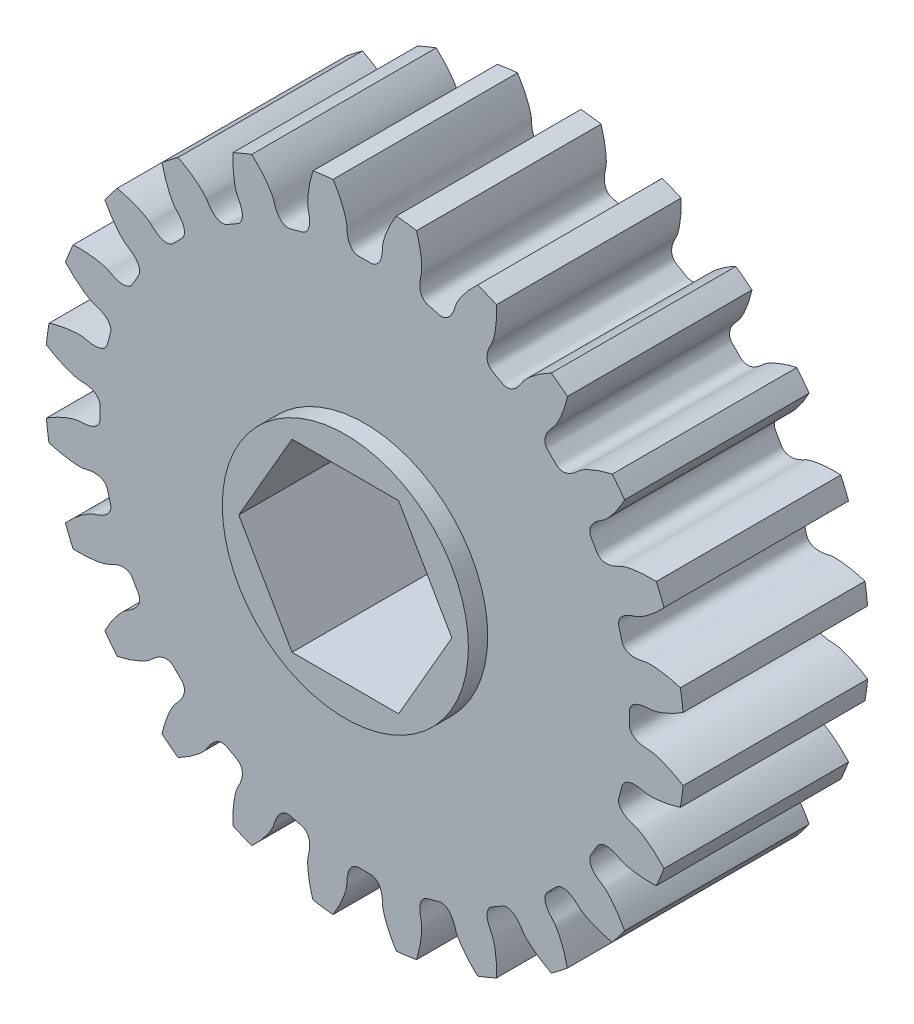
SolidWorks part; units mm, degrees
material "7075-T6 (SN)"
ref_plane "Front Plane" through (0, 0, 0) normal (0, 0, 1) x (1, 0, 0)
ref_plane "Top Plane" through (0, 0, 0) normal (0, 1, 0) x (1, 0, 0)
ref_plane "Right Plane" through (0, 0, 0) normal (1, 0, 0) x (0, 0, -1)
ref_plane "Plane1" through (0, 0, -5.715) normal (0, 0, -1) x (-1, 0, 0)
sketch "Sketch1" plane through (0, 0, -5.715) normal (0, 0, -1) x (-1, 0, 0)
  arc A0 (-12.7729, 10.461) -> (-13.4104, 9.6302) centre (0, 0) ccw
  arc A1 (-15.0452, 6.7987) -> (-15.446, 5.8312) centre (0, 0) ccw
  arc A2 (-16.2922, 2.673) -> (-16.4289, 1.6348) centre (0, 0) ccw
  arc A3 (-16.4289, -1.6348) -> (-16.2922, -2.673) centre (0, 0) ccw
  arc A4 (-15.446, -5.8312) -> (-15.0452, -6.7987) centre (0, 0) ccw
  arc A5 (-13.4104, -9.6302) -> (-12.7729, -10.461) centre (0, 0) ccw
  arc A6 (-10.461, -12.7729) -> (-9.6302, -13.4104) centre (0, 0) ccw
  arc A7 (-6.7987, -15.0452) -> (-5.8312, -15.446) centre (0, 0) ccw
  arc A8 (-2.673, -16.2922) -> (-1.6348, -16.4289) centre (0, 0) ccw
  arc A9 (1.6348, -16.4289) -> (2.673, -16.2922) centre (0, 0) ccw
  arc A10 (5.8312, -15.446) -> (6.7987, -15.0452) centre (0, 0) ccw
  arc A11 (9.6302, -13.4104) -> (10.461, -12.7729) centre (0, 0) ccw
  arc A12 (12.7729, -10.461) -> (13.4104, -9.6302) centre (0, 0) ccw
  arc A13 (15.0452, -6.7987) -> (15.446, -5.8312) centre (0, 0) ccw
  arc A14 (16.2922, -2.673) -> (16.4289, -1.6348) centre (0, 0) ccw
  arc A15 (16.4289, 1.6348) -> (16.2922, 2.673) centre (0, 0) ccw
  arc A16 (15.446, 5.8312) -> (15.0452, 6.7987) centre (0, 0) ccw
  arc A17 (13.4104, 9.6302) -> (12.7729, 10.461) centre (0, 0) ccw
  arc A18 (10.461, 12.7729) -> (9.6302, 13.4104) centre (0, 0) ccw
  arc A19 (6.7987, 15.0452) -> (5.8312, 15.446) centre (0, 0) ccw
  arc A20 (2.673, 16.2922) -> (1.6348, 16.4289) centre (0, 0) ccw
  arc A21 (-1.6348, 16.4289) -> (-2.673, 16.2922) centre (0, 0) ccw
  arc A22 (-5.8312, 15.446) -> (-6.7987, 15.0452) centre (0, 0) ccw
  arc A23 (-9.6302, 13.4104) -> (-10.461, 12.7729) centre (0, 0) ccw
  spline S0 degree 3 number of poles 101 (-15.0452, 6.7987) -> (-13.4104, 9.6302)
  spline S1 degree 3 number of poles 101 (-16.2922, 2.673) -> (-15.446, 5.8312)
  spline S2 degree 3 number of poles 101 (-16.4289, -1.6348) -> (-16.4289, 1.6348)
  spline S3 degree 3 number of poles 101 (-15.446, -5.8312) -> (-16.2922, -2.673)
  spline S4 degree 3 number of poles 101 (-13.4104, -9.6302) -> (-15.0452, -6.7987)
  spline S5 degree 3 number of poles 101 (-10.461, -12.7729) -> (-12.7729, -10.461)
  spline S6 degree 3 number of poles 101 (-6.7987, -15.0452) -> (-9.6302, -13.4104)
  spline S7 degree 3 number of poles 101 (-2.673, -16.2922) -> (-5.8312, -15.446)
  spline S8 degree 3 number of poles 101 (1.6348, -16.4289) -> (-1.6348, -16.4289)
  spline S9 degree 3 number of poles 101 (5.8312, -15.446) -> (2.673, -16.2922)
  spline S10 degree 3 number of poles 101 (9.6302, -13.4104) -> (6.7987, -15.0452)
  spline S11 degree 3 number of poles 101 (12.7729, -10.461) -> (10.461, -12.7729)
  spline S12 degree 3 number of poles 101 (15.0452, -6.7987) -> (13.4104, -9.6302)
  spline S13 degree 3 number of poles 101 (16.2922, -2.673) -> (15.446, -5.8312)
  spline S14 degree 3 number of poles 101 (16.4289, 1.6348) -> (16.4289, -1.6348)
  spline S15 degree 3 number of poles 101 (15.446, 5.8312) -> (16.2922, 2.673)
  spline S16 degree 3 number of poles 101 (13.4104, 9.6302) -> (15.0452, 6.7987)
  spline S17 degree 3 number of poles 101 (10.461, 12.7729) -> (12.7729, 10.461)
  spline S18 degree 3 number of poles 101 (6.7987, 15.0452) -> (9.6302, 13.4104)
  spline S19 degree 3 number of poles 101 (2.673, 16.2922) -> (5.8312, 15.446)
  spline S20 degree 3 number of poles 101 (-1.6348, 16.4289) -> (1.6348, 16.4289)
  spline S21 degree 3 number of poles 101 (-5.8312, 15.446) -> (-2.673, 16.2922)
  spline S22 degree 3 number of poles 101 (-9.6302, 13.4104) -> (-6.7987, 15.0452)
  spline S23 degree 3 number of poles 101 (-12.7729, 10.461) -> (-10.461, 12.7729)
extrude "Boss-Extrude1" add sketch "Sketch1" against normal blind 11.43
sketch "Sketch3" plane through (0, 0, 5.715) normal (0, 0, 1) x (1, 0, 0)
  circle A0 centre (0, 0) radius 6.35
  dimension "D1" = 12.7
extrude "Boss-Extrude3" add sketch "Sketch3" along normal blind 0.6096
sketch "Sketch4" plane through (0, 0, 6.3246) normal (0, 0, 1) x (1, 0, 0)
  line L1 (2.7496, 4.7625) -> (-2.7496, 4.7625)
  line L2 (-2.7496, 4.7625) -> (-5.4993, 0)
  line L3 (-5.4993, 0) -> (-2.7496, -4.7625)
  line L4 (-2.7496, -4.7625) -> (2.7496, -4.7625)
  line L5 (2.7496, -4.7625) -> (5.4993, 0)
  line L6 (5.4993, 0) -> (2.7496, 4.7625)
  circle A2 centre (0, 0) radius 4.7625 construction
  dimension "D1" = 9.525
extrude "Cut-Extrude1" cut sketch "Sketch4" against normal through all
sketch "Sketch5" plane through (0, 0, 6.3246) normal (0, 0, 1) x (1, 0, 0)
  arc A24 (10.461, 12.7729) -> (9.6302, 13.4104) centre (0, 0) ccw
  arc A25 (6.7987, 15.0452) -> (5.8312, 15.446) centre (0, 0) ccw
  arc A26 (2.673, 16.2922) -> (1.6348, 16.4289) centre (0, 0) ccw
  arc A27 (-1.6348, 16.4289) -> (-2.673, 16.2922) centre (0, 0) ccw
  arc A28 (-5.8312, 15.446) -> (-6.7987, 15.0452) centre (0, 0) ccw
  arc A29 (-9.6302, 13.4104) -> (-10.461, 12.7729) centre (0, 0) ccw
  arc A30 (-12.7729, 10.461) -> (-13.4104, 9.6302) centre (0, 0) ccw
  arc A31 (-15.0452, 6.7987) -> (-15.446, 5.8312) centre (0, 0) ccw
  arc A32 (-16.2922, 2.673) -> (-16.4289, 1.6348) centre (0, 0) ccw
  arc A33 (-16.4289, -1.6348) -> (-16.2922, -2.673) centre (0, 0) ccw
  arc A34 (-15.446, -5.8312) -> (-15.0452, -6.7987) centre (0, 0) ccw
  arc A35 (-13.4104, -9.6302) -> (-12.7729, -10.461) centre (0, 0) ccw
  arc A36 (-10.461, -12.7729) -> (-9.6302, -13.4104) centre (0, 0) ccw
  arc A37 (-6.7987, -15.0452) -> (-5.8312, -15.446) centre (0, 0) ccw
  arc A38 (-2.673, -16.2922) -> (-1.6348, -16.4289) centre (0, 0) ccw
  arc A39 (1.6348, -16.4289) -> (2.673, -16.2922) centre (0, 0) ccw
  arc A40 (5.8312, -15.446) -> (6.7987, -15.0452) centre (0, 0) ccw
  arc A41 (9.6302, -13.4104) -> (10.461, -12.7729) centre (0, 0) ccw
  arc A42 (12.7729, -10.461) -> (13.4104, -9.6302) centre (0, 0) ccw
  arc A43 (15.0452, -6.7987) -> (15.446, -5.8312) centre (0, 0) ccw
  arc A44 (16.2922, -2.673) -> (16.4289, -1.6348) centre (0, 0) ccw
  arc A45 (16.4289, 1.6348) -> (16.2922, 2.673) centre (0, 0) ccw
  arc A46 (15.446, 5.8312) -> (15.0452, 6.7987) centre (0, 0) ccw
  arc A47 (13.4104, 9.6302) -> (12.7729, 10.461) centre (0, 0) ccw
  arc A48 (10.461, 12.7729) -> (9.6302, 13.4104) centre (0, 0) ccw
  arc A49 (6.7987, 15.0452) -> (5.8312, 15.446) centre (0, 0) ccw
  arc A50 (2.673, 16.2922) -> (1.6348, 16.4289) centre (0, 0) ccw
  arc A51 (-1.6348, 16.4289) -> (-2.673, 16.2922) centre (0, 0) ccw
  arc A52 (-5.8312, 15.446) -> (-6.7987, 15.0452) centre (0, 0) ccw
  arc A53 (-9.6302, 13.4104) -> (-10.461, 12.7729) centre (0, 0) ccw
  arc A54 (-12.7729, 10.461) -> (-13.4104, 9.6302) centre (0, 0) ccw
  arc A55 (-15.0452, 6.7987) -> (-15.446, 5.8312) centre (0, 0) ccw
  arc A56 (-16.2922, 2.673) -> (-16.4289, 1.6348) centre (0, 0) ccw
  arc A57 (-16.4289, -1.6348) -> (-16.2922, -2.673) centre (0, 0) ccw
  arc A58 (-15.446, -5.8312) -> (-15.0452, -6.7987) centre (0, 0) ccw
  arc A59 (-13.4104, -9.6302) -> (-12.7729, -10.461) centre (0, 0) ccw
  arc A60 (-10.461, -12.7729) -> (-9.6302, -13.4104) centre (0, 0) ccw
  arc A61 (-6.7987, -15.0452) -> (-5.8312, -15.446) centre (0, 0) ccw
  arc A62 (-2.673, -16.2922) -> (-1.6348, -16.4289) centre (0, 0) ccw
  arc A63 (1.6348, -16.4289) -> (2.673, -16.2922) centre (0, 0) ccw
  arc A64 (5.8312, -15.446) -> (6.7987, -15.0452) centre (0, 0) ccw
  arc A65 (9.6302, -13.4104) -> (10.461, -12.7729) centre (0, 0) ccw
  arc A66 (12.7729, -10.461) -> (13.4104, -9.6302) centre (0, 0) ccw
  arc A67 (15.0452, -6.7987) -> (15.446, -5.8312) centre (0, 0) ccw
  arc A68 (16.2922, -2.673) -> (16.4289, -1.6348) centre (0, 0) ccw
  arc A69 (16.4289, 1.6348) -> (16.2922, 2.673) centre (0, 0) ccw
  arc A70 (15.446, 5.8312) -> (15.0452, 6.7987) centre (0, 0) ccw
  arc A71 (13.4104, 9.6302) -> (12.7729, 10.461) centre (0, 0) ccw
  spline S24 degree 3 number of poles 101 (12.7729, 10.461) -> (10.461, 12.7729)
  spline S25 degree 3 number of poles 101 (9.6302, 13.4104) -> (6.7987, 15.0452)
  spline S26 degree 3 number of poles 101 (5.8312, 15.446) -> (2.673, 16.2922)
  spline S27 degree 3 number of poles 101 (1.6348, 16.4289) -> (-1.6348, 16.4289)
  spline S28 degree 3 number of poles 101 (-2.673, 16.2922) -> (-5.8312, 15.446)
  spline S29 degree 3 number of poles 101 (-6.7987, 15.0452) -> (-9.6302, 13.4104)
  spline S30 degree 3 number of poles 101 (-10.461, 12.7729) -> (-12.7729, 10.461)
  spline S31 degree 3 number of poles 101 (-13.4104, 9.6302) -> (-15.0452, 6.7987)
  spline S32 degree 3 number of poles 101 (-15.446, 5.8312) -> (-16.2922, 2.673)
  spline S33 degree 3 number of poles 101 (-16.4289, 1.6348) -> (-16.4289, -1.6348)
  spline S34 degree 3 number of poles 101 (-16.2922, -2.673) -> (-15.446, -5.8312)
  spline S35 degree 3 number of poles 101 (-15.0452, -6.7987) -> (-13.4104, -9.6302)
  spline S36 degree 3 number of poles 101 (-12.7729, -10.461) -> (-10.461, -12.7729)
  spline S37 degree 3 number of poles 101 (-9.6302, -13.4104) -> (-6.7987, -15.0452)
  spline S38 degree 3 number of poles 101 (-5.8312, -15.446) -> (-2.673, -16.2922)
  spline S39 degree 3 number of poles 101 (-1.6348, -16.4289) -> (1.6348, -16.4289)
  spline S40 degree 3 number of poles 101 (2.673, -16.2922) -> (5.8312, -15.446)
  spline S41 degree 3 number of poles 101 (6.7987, -15.0452) -> (9.6302, -13.4104)
  spline S42 degree 3 number of poles 101 (10.461, -12.7729) -> (12.7729, -10.461)
  spline S43 degree 3 number of poles 101 (13.4104, -9.6302) -> (15.0452, -6.7987)
  spline S44 degree 3 number of poles 101 (15.446, -5.8312) -> (16.2922, -2.673)
  spline S45 degree 3 number of poles 101 (16.4289, -1.6348) -> (16.4289, 1.6348)
  spline S46 degree 3 number of poles 101 (16.2922, 2.673) -> (15.446, 5.8312)
  spline S47 degree 3 number of poles 101 (15.0452, 6.7987) -> (13.4104, 9.6302)
  spline S48 degree 3 number of poles 101 (12.7729, 10.461) -> (10.461, 12.7729)
  spline S49 degree 3 number of poles 101 (9.6302, 13.4104) -> (6.7987, 15.0452)
  spline S50 degree 3 number of poles 101 (5.8312, 15.446) -> (2.673, 16.2922)
  spline S51 degree 3 number of poles 101 (1.6348, 16.4289) -> (-1.6348, 16.4289)
  spline S52 degree 3 number of poles 101 (-2.673, 16.2922) -> (-5.8312, 15.446)
  spline S53 degree 3 number of poles 101 (-6.7987, 15.0452) -> (-9.6302, 13.4104)
  spline S54 degree 3 number of poles 101 (-10.461, 12.7729) -> (-12.7729, 10.461)
  spline S55 degree 3 number of poles 101 (-13.4104, 9.6302) -> (-15.0452, 6.7987)
  spline S56 degree 3 number of poles 101 (-15.446, 5.8312) -> (-16.2922, 2.673)
  spline S57 degree 3 number of poles 101 (-16.4289, 1.6348) -> (-16.4289, -1.6348)
  spline S58 degree 3 number of poles 101 (-16.2922, -2.673) -> (-15.446, -5.8312)
  spline S59 degree 3 number of poles 101 (-15.0452, -6.7987) -> (-13.4104, -9.6302)
  spline S60 degree 3 number of poles 101 (-12.7729, -10.461) -> (-10.461, -12.7729)
  spline S61 degree 3 number of poles 101 (-9.6302, -13.4104) -> (-6.7987, -15.0452)
  spline S62 degree 3 number of poles 101 (-5.8312, -15.446) -> (-2.673, -16.2922)
  spline S63 degree 3 number of poles 101 (-1.6348, -16.4289) -> (1.6348, -16.4289)
  spline S64 degree 3 number of poles 101 (2.673, -16.2922) -> (5.8312, -15.446)
  spline S65 degree 3 number of poles 101 (6.7987, -15.0452) -> (9.6302, -13.4104)
  spline S66 degree 3 number of poles 101 (10.461, -12.7729) -> (12.7729, -10.461)
  spline S67 degree 3 number of poles 101 (13.4104, -9.6302) -> (15.0452, -6.7987)
  spline S68 degree 3 number of poles 101 (15.446, -5.8312) -> (16.2922, -2.673)
  spline S69 degree 3 number of poles 101 (16.4289, -1.6348) -> (16.4289, 1.6348)
  spline S70 degree 3 number of poles 101 (16.2922, 2.673) -> (15.446, 5.8312)
  spline S71 degree 3 number of poles 101 (15.0452, 6.7987) -> (13.4104, 9.6302)
  circle M55 centre (0, 0) radius 6.35
  dimension "D1" = 0
extrude "Cut-Extrude2" cut sketch "Sketch5" against normal blind 2.5146 contours A70 S71 A71 S48 A48 S49 A49 S50 A50 S51 A51 S52 A52 S53 A53 S54 A54 S55 A55 S56 A56 S57 A57 S58 A58 S59 A59 S60 A60 S61 A61 S62 A62 S63 A63 S64 A64 S65 A65 S66 A66 S67 A67 S68 A68 S69 A69 S70 M55 region at (9.3342, 9.3342, 6.3246)
extrude "Cut-Extrude3" cut sketch "Sketch5<3>" against normal blind 1.5146
sketch "Sketch5<3>" plane through (0, 0, 6.3246) normal (0, 0, 1) x (1, 0, 0) same geometry as "Sketch5"
equation "\"D1@Cut-Extrude3\"=0.099in-1mm"
